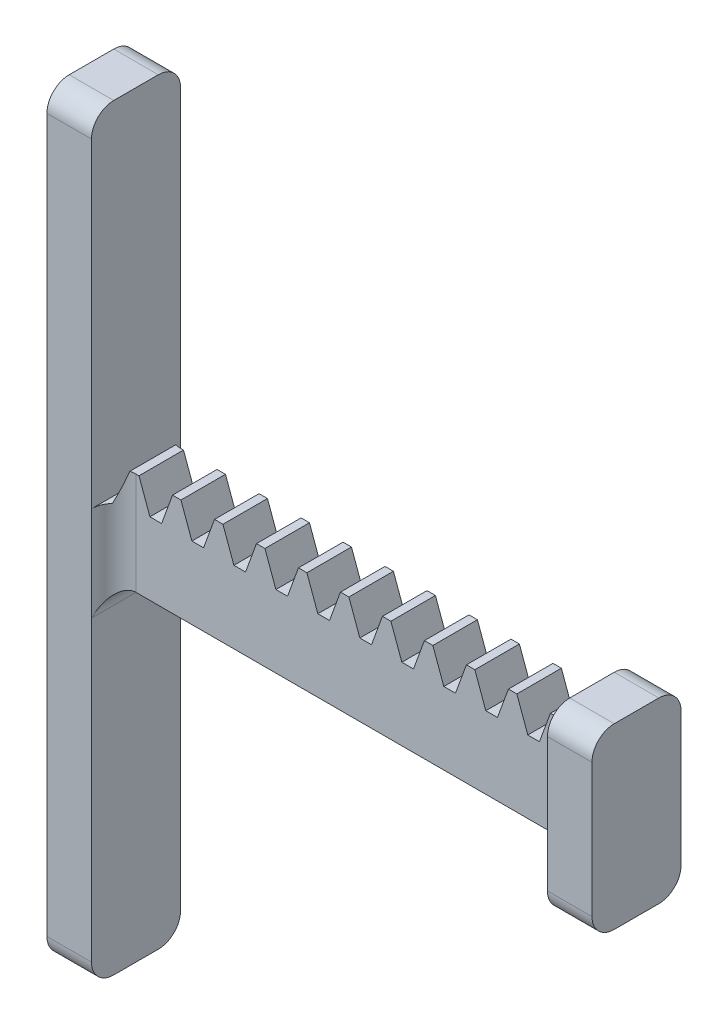
SolidWorks part; units mm, degrees
extrude "Blank" add sketch "BlankSke" against normal blind 5
sketch "BlankSke" plane through (0, 0, 0) normal (0, 0, 1) x (1, 0, 0)
  line L1 (0, 0) -> (100, 0)
  line L2 (0, 0) -> (0, 11.5)
  line L3 (0, 11.5) -> (100, 11.5)
  line L4 (100, 0) -> (100, 11.5)
  dimension "Length" = 100
ref_plane "Plane1" through (0, 0, 0) normal (0, 0, 1) x (1, 0, 0)
ref_plane "Plane2" through (0, 0, 0) normal (0, 1, 0) x (1, 0, 0)
ref_plane "Plane3" through (0, 0, 0) normal (1, 0, 0) x (0, 0, -1)
other "Configuration Table"
sketch "HoldingSke" plane through (0, 0, 0) normal (0, 1, 0) x (1, 0, 0)
  line L0 (0, 0) -> (0.0928, 0.6602)
  line L1 (-15, 0) -> (100, 0) construction
  line L2 (0, 0) -> (-2.1039, 2.3779)
  line L3 (0, 0) -> (-11.863, 4.5341)
  line L4 (0, 0) -> (7.9495, 3.3743)
  line L5 (0, 0) -> (-23.7986, -8.8762)
  line L6 (0, 0) -> (-10.5278, -7.1032)
  line L9 (-71.009, 38.7566) -> (22.9603, 72.9586)
  line L10 (-76.2, 3.8779) -> (-66.2, 3.8779)
  line L11 (0, 0) -> (-5, 0)
  line L12 (-76.2, 101.6) -> (-76.147, 101.6)
  line L13 (24.9733, 27.94) -> (52.9518, 28.4284)
  line L14 (24.9733, 27.94) -> (24.9743, 27.94)
  line L15 (24.9733, 27.94) -> (100.4006, 29.5858)
  circle A0 centre (0, 0) radius 19.05
  circle A1 centre (0, 0) radius 5
  circle A2 centre (0, 0) radius 12.7
  dimension "Num_teeth" = 23
  dimension "Width" = 5
  dimension "Length" = 100
  dimension "Pitch_height" = 10
sketch "TooCutSkeIll" plane through (0, 0, 0) normal (0, 0, 1) x (1, 0, 0)
  line L0 (-1.8687, 11.4605) -> (-0.7447, 8.3724)
  line L1 (-0.3914, 8.125) -> (0.3914, 8.125)
  line L2 (0.7447, 8.3724) -> (1.8687, 11.4605)
  line L3 (100, 11.5) -> (0, 11.5) construction
  line L4 (0, 0) -> (0, 64.897) construction
  line L5 (-13.208, 10) -> (12.954, 10) construction
  line L6 (0, 0) -> (100, 0) construction
  line L7 (1.3371, 10) -> (1.3371, 48.7463) construction
  line L8 (-1.3371, 10) -> (-1.3371, 48.7463) construction
  line L9 (1.9251, 11.5) -> (1.9251, 11.5254)
  line L10 (-1.9251, 11.5) -> (-1.9251, 11.5254)
  line L11 (-1.9251, 11.5254) -> (1.9251, 11.5254)
  arc A0 (0.3914, 8.125) -> (0.7447, 8.3724) centre (0.3914, 8.501) ccw
  arc A1 (-0.7447, 8.3724) -> (-0.3914, 8.125) centre (-0.3914, 8.501) ccw
  arc A2 (1.9251, 11.5) -> (1.8687, 11.4605) centre (1.9251, 11.44) ccw
  arc A3 (-1.8687, 11.4605) -> (-1.9251, 11.5) centre (-1.9251, 11.44) ccw
  dimension "Addendum_plus" = 1.5254
  dimension "Pitch_height" = 10
  dimension "Pressure_angle" = 20
  dimension "Gap_width" = 2.6742
  dimension "Dedendum" = 1.875
extrude "ToothCutIll" [suppressed] cut sketch "TooCutSkeIll" against normal through all
sketch "TooCutSkeSim" plane through (0, 0, 0) normal (0, 0, 1) x (1, 0, 0)
  line L0 (0.6547, 8.125) -> (-0.6547, 8.125)
  line L1 (1.8923, 11.5254) -> (0.6547, 8.125)
  line L2 (0, 17.4625) -> (0, 53.467) construction
  line L3 (1.8923, 11.5254) -> (-1.8923, 11.5254)
  line L6 (-1.8923, 11.5254) -> (-0.6547, 8.125)
  line L9 (-1.3371, 10) -> (1.3371, 10) construction
  line L10 (0, 0) -> (100, 0) construction
  line L11 (1.3371, 10) -> (1.3371, 53.467) construction
  line L12 (-1.3371, 10) -> (-1.3371, 53.467) construction
  dimension "Addendum_plus" = 1.5254
  dimension "Pitch_height" = 10
  dimension "Pressure_angle" = 20
  dimension "Gap_width" = 2.6742
  dimension "Dedendum" = 1.875
extrude "ToothCutSim" cut sketch "TooCutSkeSim" against normal through all
pattern_linear "TeethCuts" count 23 spacing 4.7124 along (1, 0, 0) of "ToothCutIll", "ToothCutSim"
sketch "Esquisse1" plane through (100, 0, 0) normal (1, 0, 0) x (0, 0, -1)
  line L0 (5, 12.1833) -> (0, 12.1833)
  line L1 (-3, 9.1833) -> (-3, 0)
  line L2 (0, -3) -> (5, -3)
  line L3 (8, 0) -> (8, 9.1833)
  line L4 (5, 9.1833) -> (0, 9.1833)
  line L5 (0, 9.1833) -> (0, 0)
  line L6 (0, 0) -> (5, 0)
  line L7 (5, 0) -> (5, 9.1833)
  line L8 (5, 9.1833) -> (0, 9.1833)
  line L9 (0, 9.1833) -> (0, 0) construction
  line L10 (0, 0) -> (5, 0)
  line L11 (5, 0) -> (5, 9.1833)
  line L12 (8, 12.1833) -> (-3, 12.1833) construction
  line L13 (8, -3) -> (8, 12.1833) construction
  line L14 (-3, -3) -> (8, -3) construction
  line L15 (-3, 12.1833) -> (-3, -3) construction
  arc A0 (5, 12.1833) -> (8, 9.1833) centre (5, 9.1833) cw
  arc A1 (5, -3) -> (8, 0) centre (5, 0) ccw
  arc A2 (-3, 0) -> (0, -3) centre (0, 0) ccw
  arc A3 (0, 12.1833) -> (-3, 9.1833) centre (0, 9.1833) ccw
  line M9 (5, 9.1833) -> (0, 9.1833)
  line M10 (0, 9.1833) -> (0, 0)
  line M11 (0, 0) -> (5, 0)
  line M12 (5, 0) -> (5, 9.1833)
  dimension "D3" = 3
  dimension "D1" = 0
  dimension "D2" = 3
extrude "Boss.-Extru.1" add sketch "Esquisse1" along normal blind 5 contours M12 M9 M10 M11 | L2 L3 L0 L1 M9 M12 M11 M10 region at (100, 11.172, -6.9887) region at (100, 4.5916, -2.5)
sketch "Esquisse2" plane through (0, 0, 0) normal (-1, 0, 0) x (0, 0, 1)
  line L0 (-5, 8.125) -> (0, 0) construction
  line L1 (0, 8.125) -> (-5, 0) construction
  line L3 (-5, 46.5625) -> (0, 46.5625)
  line L4 (-7.5, 44.0625) -> (-7.5, -35.9375)
  line L5 (-5, -38.4375) -> (0, -38.4375)
  line L6 (2.5, 44.0625) -> (2.5, -35.9375)
  line L7 (-7.5, 46.5625) -> (2.5, -38.4375) construction
  line L8 (-7.5, -38.4375) -> (2.5, 46.5625) construction
  arc A0 (0, 46.5625) -> (2.5, 44.0625) centre (0, 44.0625) cw
  arc A1 (0, -38.4375) -> (2.5, -35.9375) centre (0, -35.9375) ccw
  arc A2 (-7.5, -35.9375) -> (-5, -38.4375) centre (-5, -35.9375) ccw
  arc A3 (-5, 46.5625) -> (-7.5, 44.0625) centre (-5, 44.0625) ccw
  point P8 (-2.5, 4.0625)
  dimension "D1" = 2.5
  dimension "D2" = 80
  dimension "D3" = 10
extrude "Boss.-Extru.2" add sketch "Esquisse2" along normal blind 5
fillet "Congé2" radius 2.5 1 edges at (0, 4.0625, -5) type face fillet first side face at (0, 4.0625, -2.5) second side face at (50.0668, 9.547, -5)
fillet "Congé3" radius 2.5 1 edges at (0, 4.0625, 0) type face fillet first side face at (50.0668, 9.547, 0) second side face at (0, 4.0625, -2.9167)
fillet "Congé4" radius 2.5 1 edges at (0, 0, -2.5) type face fillet first side face at (33.9941, 0, -2.5) second side face at (0, -24.9643, -2.5)
sketch "Esquisse4" plane through (0, 0, -5) normal (0, 0, -1) x (-1, 0, 0)
  line L1 (-105, -3) -> (-51.1744, -3)
  line L2 (-105, -3) -> (-105, 14.7743)
  line L3 (-105, 14.7743) -> (-51.1744, 14.7743)
  line L4 (-51.1744, -3) -> (-51.1744, 14.7743)
  point P5 (0, 0)
  point P6 (0, 0)
  point P7 (0, 0)
  point P8 (-105, 14.7743)
extrude "Enlèv. mat.-Extru.1" cut sketch "Esquisse4" against normal through all and the other way through all
sketch "Esquisse5" plane through (51.1744, 0, 0) normal (1, 0, 0) x (0, 0, -1)
  line L0 (0, 8.145) -> (5, 0) construction
  line L1 (0, 0) -> (5, 8.145) construction
  line L3 (0, 14.0725) -> (5, 14.0725)
  line L4 (-2.5, 11.5725) -> (-2.5, -3.4275)
  line L5 (0, -5.9275) -> (5, -5.9275)
  line L6 (7.5, 11.5725) -> (7.5, -3.4275)
  line L7 (-2.5, 14.0725) -> (7.5, -5.9275) construction
  line L8 (-2.5, -5.9275) -> (7.5, 14.0725) construction
  arc A0 (5, -5.9275) -> (7.5, -3.4275) centre (5, -3.4275) ccw
  arc A1 (-2.5, -3.4275) -> (0, -5.9275) centre (0, -3.4275) ccw
  arc A2 (5, 14.0725) -> (7.5, 11.5725) centre (5, 11.5725) cw
  arc A3 (0, 14.0725) -> (-2.5, 11.5725) centre (0, 11.5725) ccw
  point P8 (2.5, 4.0725)
  dimension "D3" = 2.5
  dimension "D1" = 20
  dimension "D2" = 10
extrude "Boss.-Extru.3" add sketch "Esquisse5" along normal blind 5
equation "' \"Module@HoldingSke\" = 6.35"
equation "' \"Num_teeth@HoldingSke\" = 12"
equation "' \"Ap@HoldingSke\" =  20"
equation "' \"Ap@HoldingSke\" = 20"
equation "' \"Width@HoldingSke\" = 0.25 * 25.4"
equation "' \"Show_teeth@HoldingSke\" = 500"
equation "' \"Backlash@HoldingSke\" = 0.009 * 25.4"
equation "' \"Addendum_fac@HoldingSke\" = 1.0"
equation "' \"Dedendum_fac@HoldingSke\" = 1.25"
equation "' \"Dedendum_add@HoldingSke\" = 0.00005 * 25.4"
equation "' \"Clearance_fac@HoldingSke\" = 0.25"
equation "' \"Pitch_height@HoldingSke\" = 1 * 25.4"
equation "' \"Length@HoldingSke\" = 4.71 * 25.4"
equation "\"Pitch@HoldingSke\" = 1 / \"Module@HoldingSke\""
equation "\"MPH@HoldingSke\" = \"Dedendum_fac@HoldingSke\" / \"Pitch@HoldingSke\" + 2 * \"Dedendum_add@HoldingSke\" + 0.002 * 25.4"
equation "\"MPH@HoldingSke\" = ((sgn( \"MPH@HoldingSke\" - \"Pitch_height@HoldingSke\")+1)*( \"MPH@HoldingSke\" - \"Pitch_height@HoldingSke\"))/2 + \"Pitch_height@HoldingSke\""
equation "\"Blank_height@BlankSke\" = \"Pitch_height@HoldingSke\" + \"Addendum_fac@HoldingSke\"  / \"Pitch@HoldingSke\" "
equation "\"Length@BlankSke\" =  \"Length@HoldingSke\""
equation "\"Face_width@Blank\" = \"Width@HoldingSke\""
equation "\"Pressure_angle@TooCutSkeIll\" = \"Ap@HoldingSke\""
equation "\"Addendum_plus@TooCutSkeIll\" =  \"Addendum_fac@HoldingSke\"  / \"Pitch@HoldingSke\" + 0.001 *25.4"
equation "\"Dedendum@TooCutSkeIll\" = \"Dedendum_fac@HoldingSke\"  / \"Pitch@HoldingSke\""
equation "\"Pitch_height@TooCutSkeIll\" =  \"MPH@HoldingSke\""
equation "\"Gap_width@TooCutSkeIll\" = 3.14159265 / 2 / \"Pitch@HoldingSke\" + 6 * \"Backlash@HoldingSke\""
equation "\"Pressure_angle@TooCutSkeSim\" = \"Ap@HoldingSke\""
equation "\"Addendum_plus@TooCutSkeSim\" =  \"Addendum_fac@HoldingSke\"  / \"Pitch@HoldingSke\" + 0.001 * 25.4"
equation "\"Dedendum@TooCutSkeSim\" = \"Dedendum_fac@HoldingSke\"  / \"Pitch@HoldingSke\""
equation "\"Pitch_height@TooCutSkeSim\" =  \"MPH@HoldingSke\""
equation "\"Gap_width@TooCutSkeSim\" = 3.14159265 / 2 / \"Pitch@HoldingSke\" + 6 * \"Backlash@HoldingSke\""
equation "\"Root_fillet@TooCutSkeIll\" = \"Clearance_fac@HoldingSke\" / \"Pitch@HoldingSke\" + \"Dedendum_add@HoldingSke\""
equation "\"Break_rad@TooCutSkeIll\" = 0.02 / \"Pitch@HoldingSke\" * 2"
equation "\"Linear_pitch@TeethCuts\" = 3.14159265 / \"Pitch@HoldingSke\""
equation "\"Num_teeth@HoldingSke\" = int( ( \"Length@HoldingSke\" + 0 ) / (3.14159265 / \"Pitch@HoldingSke\")) + 0.9999  + 1"
equation " \"Num_teeth@TeethCuts\" = int( \"Show_teeth@HoldingSke\" ) + 1"
equation " \"Num_teeth@TeethCuts\" = ((sgn( \"Num_teeth@TeethCuts\" - \"Num_teeth@HoldingSke\" )-1)*( \"Num_teeth@TeethCuts\" - \"Num_teeth@HoldingSke\" ))/-2+ \"Num_teeth@HoldingSke\""
equation " \"Num_teeth@TeethCuts\" = ((sgn( \"Num_teeth@TeethCuts\" - 2.0)+1)*( \"Num_teeth@TeethCuts\" - 2.0))/2 +2.0"
